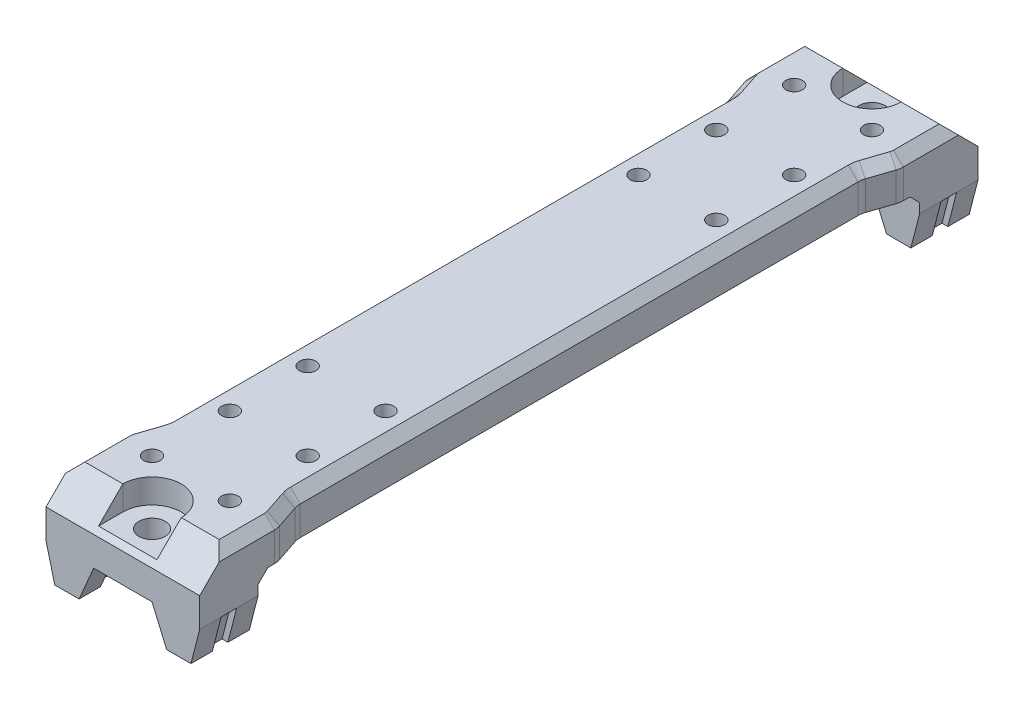
SolidWorks part; units mm, degrees
material "ABS"
ref_plane "正面" through (0, 0, 0) normal (0, 0, 1) x (1, 0, 0)
ref_plane "平面" through (0, 0, 0) normal (0, 1, 0) x (1, 0, 0)
ref_plane "右側面" through (0, 0, 0) normal (1, 0, 0) x (0, 0, -1)
sketch "ｽｹｯﾁ1" plane through (0, 0, 0) normal (0, 1, 0) x (1, 0, 0)
  line L2 (-7.9, 0) -> (-7.9, -38)
  line L3 (-7.9, -38) -> (7.9, -38)
  line L4 (7.9, 0) -> (7.9, -38)
  line L5 (-7.9, 0) -> (7.9, -38) construction
  line L6 (-7.9, -38) -> (7.9, 0) construction
  arc A0 (7.9, 0) -> (-7.9, 0) centre (0, 0) ccw
  point P7 (0, -19)
  dimension "D2" = 0
  dimension "D4" = 38
  dimension "D3" = 15.8
extrude "ﾎﾞｽ - 押し出し1" add sketch "ｽｹｯﾁ1" along normal blind 4
sketch "ｽｹｯﾁ4" plane through (0, 0, 38) normal (0, 0, 1) x (1, 0, 0)
  line L1 (-7, -5.5) -> (-4.5, -5.5)
  line L2 (-4.5, -5.5) -> (-3, -2)
  line L3 (-3, -2) -> (3, -2)
  line L4 (3, -2) -> (4.5, -5.5)
  line L5 (4.5, -5.5) -> (7, -5.5)
  line L7 (7.9, 0) -> (-7.9, 0)
  line L8 (-7, -5.5) -> (-7.9, -2)
  line L9 (-7.9, -2) -> (-7.9, 0)
  line L10 (7.9, 0) -> (7.9, -2)
  line L11 (7.9, -2) -> (7, -5.5)
  dimension "D1" = 5.5
  dimension "D2" = 3.5
  dimension "D3" = 3
  dimension "D4" = 7
  dimension "D5" = 2.5
  dimension "D9" = 2
  dimension "D10" = 2
extrude "ﾎﾞｽ - 押し出し3" add sketch "ｽｹｯﾁ4" against normal blind 6
chamfer "面取り1" distance 3 angle 45 1 edges at (0, 4, 38)
sketch "ｽｹｯﾁ5" plane through (0, 4, 0) normal (0, 1, 0) x (1, 0, 0)
  line L0 (-4, -31) -> (4, -31) construction
  line L1 (7.9, -38) -> (-7.9, -38) construction
  circle A0 centre (-4, -31) radius 0.85
  circle A1 centre (4, -31) radius 0.85
  dimension "D1" = 1.7
  dimension "D2" = 1.7
  dimension "D4" = 4
  dimension "D3" = 8
  dimension "D5" = 7
extrude "ｶｯﾄ - 押し出し1" cut sketch "ｽｹｯﾁ5" against normal blind 4
pattern_linear "直線ﾊﾟﾀｰﾝ1" count 4 spacing 8 along (0, 0, -1) of "ｶｯﾄ - 押し出し1"
sketch "ｽｹｯﾁ6" plane through (0, 4, 0) normal (0, 1, 0) x (1, 0, 0)
  line L0 (-3, -35) -> (-3, -39)
  line L1 (-3, -39) -> (3, -39)
  line L2 (3, -39) -> (3, -35)
  line L3 (7.9, -38) -> (-7.9, -38) construction
  arc A0 (3, -35) -> (-3, -35) centre (0, -35) ccw
  dimension "D1" = 6
  dimension "D3" = 3
  dimension "D2" = 0
  dimension "D4" = 4
extrude "ｶｯﾄ - 押し出し2" cut sketch "ｽｹｯﾁ6" against normal blind 2.5
sketch "ｽｹｯﾁ7" plane through (0, 1.5, 0) normal (0, 1, 0) x (1, 0, 0)
  circle A0 centre (0, -35) radius 1.35
  dimension "D1" = 2.7
extrude "ｶｯﾄ - 押し出し3" cut sketch "ｽｹｯﾁ7" against normal up to next
sketch "ｽｹｯﾁ8" plane through (0, 0, 0) normal (0, -1, 0) x (1, 0, 0)
  circle A0 centre (0, 0) radius 6
  dimension "D1" = 12
extrude "ﾎﾞｽ - 押し出し4" add sketch "ｽｹｯﾁ8" along normal blind 1.5
fillet "ﾌｨﾚｯﾄ1" radius 0.5 1 edges at (0, 0, 6)
sketch "ｽｹｯﾁ9" plane through (0, 4, 0) normal (0, 1, 0) x (1, 0, 0)
  circle A0 centre (0, 0) radius 5
  dimension "D1" = 10
extrude "ｶｯﾄ - 押し出し4" cut sketch "ｽｹｯﾁ9" against normal blind 3.6
sketch "ｽｹｯﾁ10" plane through (0, 0.4, 0) normal (0, 1, 0) x (1, 0, 0)
  circle A0 centre (0, 0) radius 3.55
  dimension "D1" = 7.1
extrude "ｶｯﾄ - 押し出し5" cut sketch "ｽｹｯﾁ10" against normal blind 3.6
ref_plane "平面1" through (0, 0, 35) normal (0, 0, 1) x (1, 0, 0)
sketch "ｽｹｯﾁ11" plane through (0, 0, 35) normal (0, 0, 1) x (1, 0, 0)
  line L0 (3, -2) -> (4.5, -5.5)
  line L1 (3, -2) -> (3.6, -2)
  line L2 (4.5, -5.5) -> (5.1, -5.5)
  line L3 (3.6, -2) -> (5.1, -5.5)
  line L4 (3, -2) -> (5.1, -5.5) construction
  line L5 (4.5, -5.5) -> (3.6, -2) construction
  line L6 (4.5, -5.5) -> (7, -5.5) construction
  line L7 (7.9, -2) -> (7, -5.5)
  line L8 (7.9, -2) -> (7.3, -2)
  line L9 (7, -5.5) -> (6.4, -5.5)
  line L10 (7.3, -2) -> (6.4, -5.5)
  line L11 (7.9, -2) -> (6.4, -5.5) construction
  line L12 (7, -5.5) -> (7.3, -2) construction
  point P5 (4.05, -3.75)
  point P14 (7.15, -3.75)
  dimension "D1" = 0.6
extrude "ｶｯﾄ - 押し出し6" cut sketch "ｽｹｯﾁ11" against normal mid plane 1.6
mirror "ﾐﾗｰ1" about plane through (0, 0, 0) normal (1, 0, 0) of "ｶｯﾄ - 押し出し6"
sketch "ｽｹｯﾁ12" plane through (0, 4, 0) normal (0, 1, 0) x (1, 0, 0)
  line L0 (-7.9, 0) -> (-7.9, -30)
  line L1 (-7.9, 0) -> (-7.9, -35) construction
  line L2 (-7.9, -30) -> (-6.9, -27)
  line L3 (-6.9, -27) -> (-6.9, -3.8471)
  line L4 (7.9, -38) -> (-7.9, -38) construction
  arc A0 (-7.9, 0) -> (-6.9, -3.8471) centre (0, 0) ccw
  arc A1 (7.9, 0) -> (-7.9, 0) centre (0, 0) ccw construction
  dimension "D1" = 6.9
  dimension "D2" = 11
  dimension "D3" = 3
extrude "ｶｯﾄ - 押し出し7" cut sketch "ｽｹｯﾁ12" against normal through all
mirror "ﾐﾗｰ2" about plane through (0, 0, 0) normal (1, 0, 0) of "ｶｯﾄ - 押し出し7"
fillet "ﾌｨﾚｯﾄ2" radius 2 6 edges at (7.9, 2, 30) (6.9, 2, 27) (6.9, 2, 3.8471) (-7.9, 2, 30) (-6.9, 2, 27) (-6.9, 2, 3.8471)
chamfer "面取り2" distance 1 angle 45 14 edges at (-7.9, 4, 32.6623) (0, 4, -7.9) (7.9, 4, 32.6623) (0, 0, 32) (-7.8742, 4, 30.0042) (-7.4, 4, 28.5) (-6.9258, 4, 26.9958) (-6.9, 4, 15.5057) (-6.9512, 4, 3.8864) (6.9512, 4, 3.8864) (6.9, 4, 15.5057) (6.9258, 4, 26.9958) (7.4, 4, 28.5) (7.8742, 4, 30.0042)
ref_plane "平面2" through (0, 0, 8) normal (0, 0, 1) x (1, 0, 0)
split "部品分割1" trim tools "平面2" bodies to split 116 resulting bodies 117
sketch "ｽｹｯﾁ14" plane through (0, 0, 8) normal (0, 0, -1) x (-1, 0, 0)
  line L0 (6.9, 0) -> (-6.9, 0)
  line L1 (-6.9, 0) -> (-6.9, 3)
  line L2 (-6.9, 3) -> (-5.9, 4)
  line L3 (-5.9, 4) -> (5.9, 4)
  line L4 (5.9, 4) -> (6.9, 3)
  line L5 (6.9, 3) -> (6.9, 0)
extrude "ﾎﾞｽ - 押し出し5" add sketch "ｽｹｯﾁ14" along normal blind 10
ref_plane "平面3" through (0, 0, -2) normal (0, 0, -1) x (-1, 0, 0)
mirror "ﾐﾗｰ3" about plane through (0, 0, -2) normal (0, 0, -1) of bodies 118
